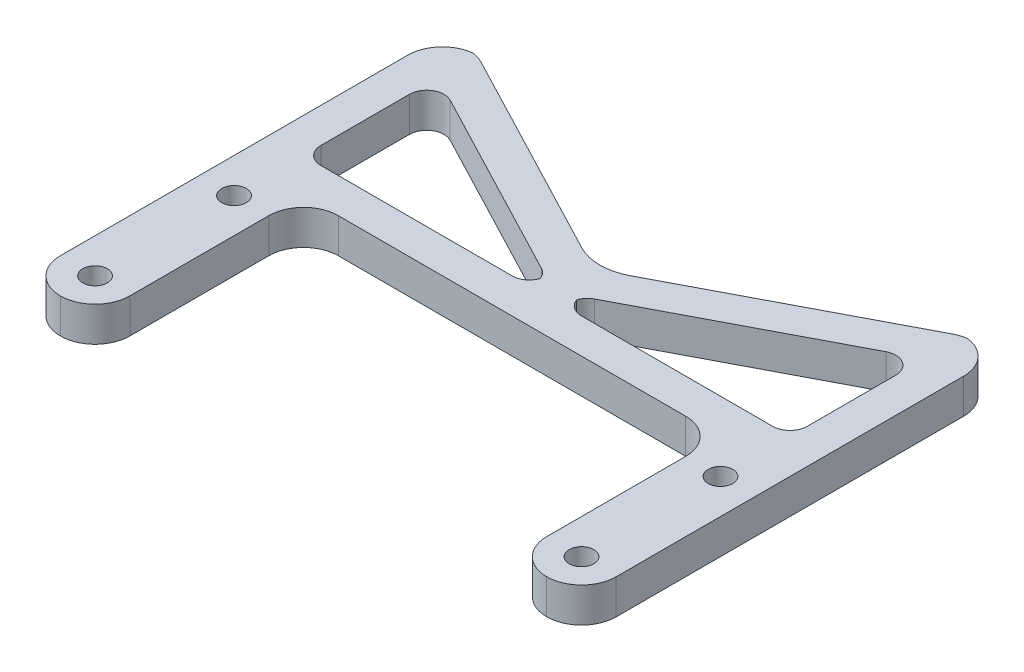
SolidWorks part; units mm, degrees
material "Custom Plastic"
ref_plane "Front Plane" through (0, 0, 0) normal (0, 0, 1) x (1, 0, 0)
ref_plane "Top Plane" through (0, 0, 0) normal (0, 1, 0) x (1, 0, 0)
ref_plane "Right Plane" through (0, 0, 0) normal (1, 0, 0) x (0, 0, -1)
sketch "Sketch1" plane through (0, 0, 0) normal (0, 1, 0) x (1, 0, 0)
  line L1 (-50.8, -38.1) -> (50.8, -38.1)
  line L2 (-50.8, -38.1) -> (-50.8, 38.1)
  line L3 (-50.8, 38.1) -> (50.8, 38.1)
  line L4 (50.8, -38.1) -> (50.8, 38.1)
  line L5 (-50.8, -38.1) -> (50.8, 38.1) construction
  line L6 (-50.8, 38.1) -> (50.8, -38.1) construction
  point P0 (0, 0)
  dimension "D1" = 101.6
  dimension "D2" = 76.2
extrude "Base" add sketch "Sketch1" along normal blind 6.35
sketch "Sketch2" plane through (0, 6.35, 0) normal (0, 1, 0) x (1, 0, 0)
  line L0 (-44.45, 38.1) -> (0, 14.8552)
  line L1 (50.8, 38.1) -> (-50.8, 38.1) construction
  line L2 (0, 14.8552) -> (44.45, 38.1)
  line L3 (-44.45, 38.1) -> (44.45, 38.1)
  line L4 (0, 0) -> (0, 38.1) construction
  circle A0 centre (0, 23.8125) radius 7.9375 construction
  dimension "D1" = 15.875
  dimension "D2" = 88.9
  dimension "D3" = 14.2875
extrude "Tube notch" cut sketch "Sketch2" against normal through all
sketch "Sketch3" plane through (0, 6.35, 0) normal (0, 1, 0) x (1, 0, 0)
  line L1 (0, 0) -> (0, -38.1) construction
  line L2 (-44.45, -6.35) -> (44.45, -6.35) construction
  line L3 (-44.45, -6.35) -> (-44.45, -31.75) construction
  line L4 (-44.45, -31.75) -> (44.45, -31.75) construction
  line L5 (44.45, -6.35) -> (44.45, -31.75) construction
  line L6 (-50.8, -38.1) -> (50.8, -38.1) construction
  line L7 (-50.8, 0) -> (50.8, 0) construction
  line L8 (-50.8, 38.1) -> (-50.8, -38.1) construction
  line L9 (50.8, -38.1) -> (50.8, 38.1) construction
  point P9 (0, -6.35)
  dimension "D1" = 88.9
  dimension "D2" = 6.35
  dimension "D3" = 25.4
  dimension "D4" = 6.35
hole_wizard "Mounting holes" positions "Sketch5" profile "Sketch4" hole size "#8" standard "ANSI Inch" end condition through all
sketch "Sketch5" plane through (0, 6.35, 0) normal (0, 1, 0) x (1, 0, 0)
  point P0 (-44.45, -6.35)
  point P3 (-44.45, -31.75)
  point P6 (44.45, -31.75)
  point P9 (44.45, -6.35)
sketch "Sketch4" plane through (-44.45, 6.35, 6.35) normal (1, 0, 0) x (0, 0, 1)
  line L0 (0, 0) -> (0, 6.35)
  line L1 (0, 6.35) -> (2.2479, 6.35)
  line L2 (2.2479, 6.35) -> (2.2479, 0)
  line L5 (2.2479, 0) -> (0, 0)
  line L11 (0, -6.35) -> (0, 107.95) construction
  dimension "Thru Hole Dia." = 4.4958
  dimension "Thru Hole Depth" = 6.35
sketch "Sketch8" plane through (0, 6.35, 0) normal (0, 1, 0) x (1, 0, 0)
  line L0 (-50.8, -38.1) -> (50.8, -38.1) construction
  line L1 (-38.1, -38.1) -> (38.1, -38.1)
  line L2 (-38.1, -38.1) -> (-38.1, 0)
  line L3 (-38.1, 0) -> (38.1, 0)
  line L4 (38.1, -38.1) -> (38.1, 0)
  point P6 (0, 0)
  dimension "D1" = 38.1
  dimension "D2" = 76.2
extrude "Wheel cutout" cut sketch "Sketch8" against normal through all
fillet "Fillet1" radius 6.35 10 edges at (-50.8, 3.175, 38.1) (-44.45, 3.175, -38.1) (44.45, 3.175, -38.1) (50.8, 3.175, -38.1) (50.8, 3.175, 38.1) (38.1, 3.175, 38.1) (38.1, 3.175, 0) (-38.1, 3.175, 0) (-38.1, 3.175, 38.1) (-50.8, 3.175, -38.1)
fillet "Fillet2" radius 9.525 1 edges at (0, 3.175, -14.8552)
sketch "Sketch9" plane through (0, 6.35, 0) normal (0, 1, 0) x (1, 0, 0)
  line L0 (-44.45, 6.35) -> (-44.45, 30.9341)
  line L1 (-44.45, 30.9341) -> (-3.175, 9.3497)
  line L2 (3.175, 9.3497) -> (44.45, 30.9341)
  line L3 (44.45, 30.9341) -> (44.45, 6.35)
  line L4 (44.45, 6.35) -> (3.175, 6.35)
  line L5 (-43.0675, 37.377) -> (-4.4139, 17.1634) construction
  line L6 (-50.8, 31.75) -> (-50.8, -31.75) construction
  line L7 (31.75, 0) -> (-31.75, 0) construction
  line L8 (-3.175, 9.3497) -> (-3.175, 6.35)
  line L9 (3.175, 9.3497) -> (3.175, 6.35)
  line L10 (-3.175, 6.35) -> (-44.45, 6.35)
  line L11 (4.4139, 17.1634) -> (43.0675, 37.377) construction
  line L12 (50.8, -31.75) -> (50.8, 31.75) construction
  dimension "D1" = 6.35
  dimension "D2" = 6.35
  dimension "D3" = 6.35
  dimension "D4" = 6.35
  dimension "D5" = 6.35
extrude "Cut-Extrude1" cut sketch "Sketch9" against normal through all
fillet "Fillet3" radius 3.175 8 edges at (-44.45, 3.175, -6.35) (-3.175, 3.175, -9.3497) (-3.175, 3.175, -6.35) (44.45, 3.175, -6.35) (3.175, 3.175, -6.35) (3.175, 3.175, -9.3497) (44.45, 3.175, -30.9341) (-44.45, 3.175, -30.9341)
equation "\"MAT_THICKNESS\"=0.1"
